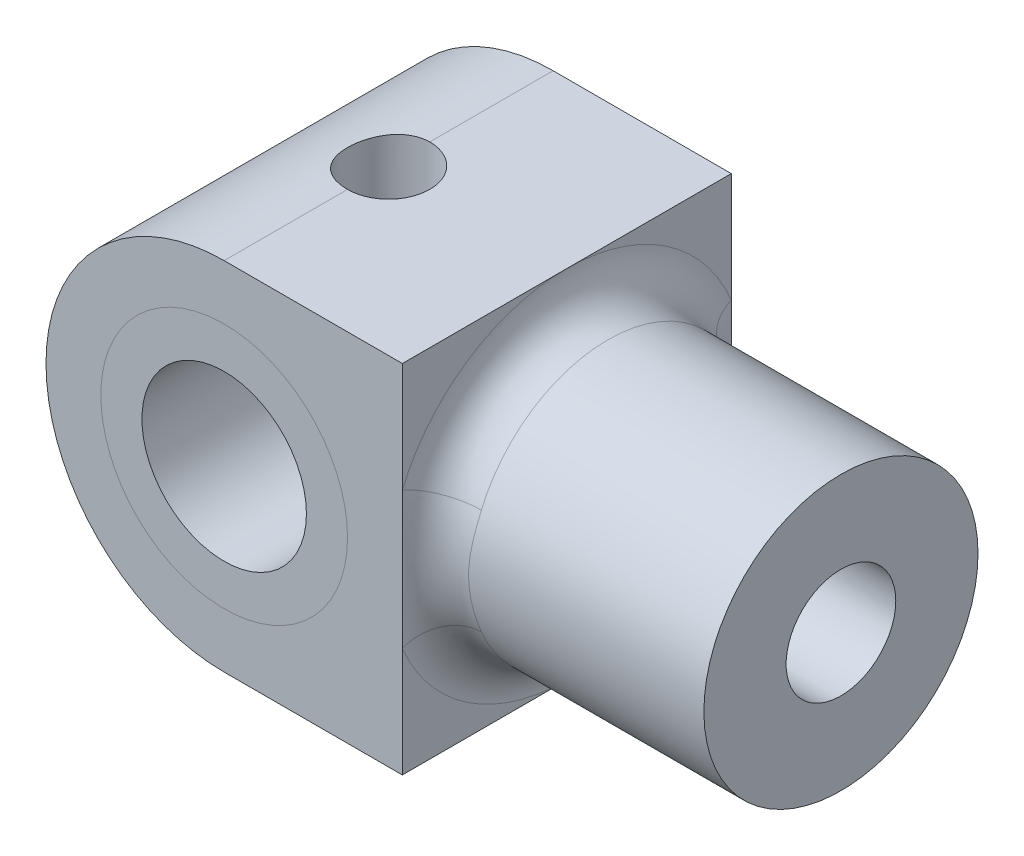
SolidWorks part; units mm, degrees
ref_plane "Front Plane" through (0, 0, 0) normal (0, 0, 1) x (1, 0, 0)
ref_plane "Top Plane" through (0, 0, 0) normal (0, 1, 0) x (1, 0, 0)
ref_plane "Right Plane" through (0, 0, 0) normal (1, 0, 0) x (0, 0, -1)
sketch "Sketch1" plane through (0, 0, 0) normal (0, 0, 1) x (1, 0, 0)
  line L0 (0, 0) -> (-11815.5821, 0) construction
  line L1 (0, 0) -> (0, -11815.5821) construction
  line L3 (6.5, 6.5) -> (0, 6.5)
  line L4 (6.5, 6.5) -> (6.5, -6.5)
  line L5 (6.5, -6.5) -> (0, -6.5)
  line L7 (6.5, 6.5) -> (0, -6.5) construction
  line L8 (6.5, -6.5) -> (0, 6.5) construction
  circle A0 centre (0, 0) radius 3
  circle A1 centre (0, 0) radius 4.5
  arc A2 (0, -6.5) -> (0, 6.5) centre (0, 0) cw
  point P8 (3.25, 0)
  point P13 (-6.5, 0)
  dimension "D1" = 9
  dimension "6" = 6
  dimension "D2" = 6.5
  dimension "D3" = 13
extrude "Boss-Extrude1" add sketch "Sketch1" along normal mid plane 12 contours A2 L5 L4 L3 A1 region at (6.3162, 0, 0)
sketch "Sketch2" plane through (6.5, 0, 0) normal (1, 0, 0) x (0, 0, -1)
  circle A0 centre (0, 0) radius 5
  circle A1 centre (0, 0) radius 2
  dimension "D1" = 10
  dimension "D2" = 4
extrude "Boss-Extrude2" add sketch "Sketch2" along normal blind 10 contours A0 region at (6.5, 0, 4.8586)
cosmetic thread "Cosmetic Thread1" parameters "D2"=5
fillet "Fillet1" radius 1.5 1 edges at (6.5, 0, -5)
extrude "Boss-Extrude3" add sketch "Sketch1<3>" along normal mid plane 12 separate body contours A1 A0 region at (-4.3727, 0, 0)
sketch "Sketch1<3>" plane through (0, 0, 0) normal (0, 0, 1) x (1, 0, 0) same geometry as "Sketch1"
sketch "Sketch3" plane through (0, 0, 0) normal (0, 1, 0) x (1, 0, 0)
  circle A0 centre (0, 0) radius 1.5
  dimension "D1" = 3
extrude "Cut-Extrude1" cut sketch "Sketch3" along normal through all
